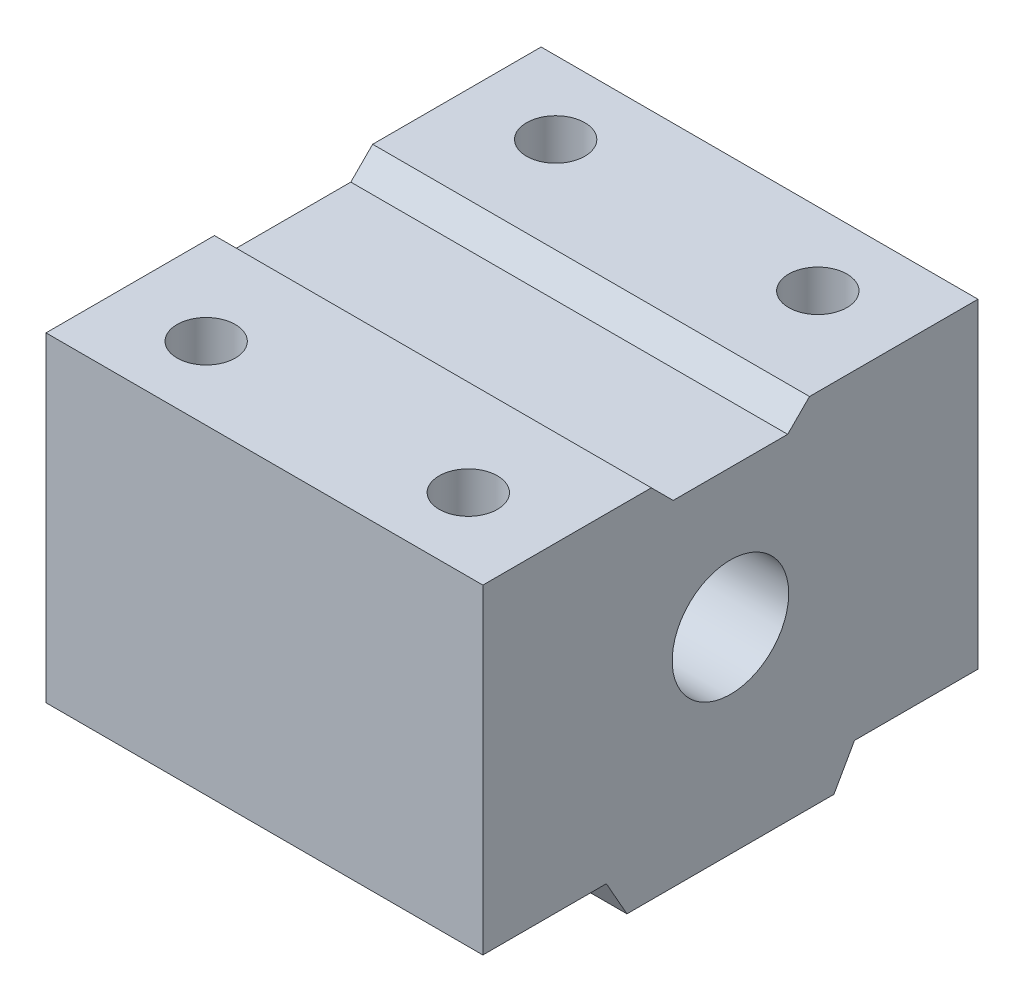
SolidWorks part; units mm, degrees
ref_plane "Front Plane" through (0, 0, 0) normal (0, 0, 1) x (1, 0, 0)
ref_plane "Top Plane" through (0, 0, 0) normal (0, 1, 0) x (1, 0, 0)
ref_plane "Right Plane" through (0, 0, 0) normal (1, 0, 0) x (0, 0, -1)
sketch "Sketch1" plane through (0, 0, 0) normal (0, 1, 0) x (1, 0, 0)
  line L1 (-15, 17) -> (15, 17)
  line L2 (-15, 17) -> (-15, -17)
  line L3 (-15, -17) -> (15, -17)
  line L4 (15, 17) -> (15, -17)
  line L5 (-15, 17) -> (15, -17) construction
  line L6 (-15, -17) -> (15, 17) construction
  point P0 (0, 0)
  dimension "D1" = 30
  dimension "D2" = 34
extrude "Boss-Extrude1" add sketch "Sketch1" along normal blind 22
hole_wizard "Ø4.0mm Dowel Hole1" positions "Sketch2" profile "Sketch3" hole size "Ø4.0" standard "ANSI Metric" end condition up to next
sketch "Sketch2" plane through (0, 22, 0) normal (0, 1, 0) x (1, 0, 0)
  line L0 (-15, 0) -> (15, 0) construction
  line L1 (-15, 17) -> (-15, -17) construction
  line L2 (15, 17) -> (15, -17) construction
  line L4 (0, 0) -> (0, -17) construction
  line L5 (-15, -17) -> (15, -17) construction
  point P0 (9, -12)
  point P2 (-9, -12)
  point P19 (9, 12)
  point P20 (-9, 12)
  dimension "D1" = 12
  dimension "D2" = 12
  dimension "D3" = 9
  dimension "D4" = 9
sketch "Sketch3" plane through (9, 22, 12) normal (1, 0, 0) x (0, 0, 1)
  line L0 (0, 0) -> (0, 22)
  line L1 (0, 22) -> (2, 22)
  line L2 (2, 22) -> (2, 0)
  line L5 (2, 0) -> (0, 0)
  line L11 (0, -6.35) -> (0, 107.95) construction
  dimension "Thru Hole Dia." = 4
  dimension "Thru Hole Depth" = 22
sketch "Sketch4" plane through (15, 0, 0) normal (1, 0, 0) x (0, 0, -1)
  line L0 (-8.5198, 0) -> (8.5198, 0)
  line L1 (-17, 0) -> (17, 0) construction
  line L2 (17, 0) -> (-17, 0) construction
  line L3 (8.5198, 0) -> (7.1062, -2.5)
  line L4 (7.1062, -2.5) -> (-7.1062, -2.5)
  line L5 (0, 0) -> (0, -2.5) construction
  line L6 (-8.5198, 0) -> (-7.1062, -2.5)
  dimension "D1" = 2.5
extrude "Boss-Extrude2" add sketch "Sketch4" against normal through all
sketch "Sketch5" plane through (0, 22, 0) normal (0, 1, 0) x (1, 0, 0)
  line L1 (-15, 5.4305) -> (15, 5.4305)
  line L2 (-15, 5.4305) -> (-15, -5.4305)
  line L3 (-15, -5.4305) -> (15, -5.4305)
  line L4 (15, 5.4305) -> (15, -5.4305)
  line L5 (-15, 5.4305) -> (15, -5.4305) construction
  line L6 (-15, -5.4305) -> (15, 5.4305) construction
  line L7 (15, 17) -> (15, -17) construction
extrude "Cut-Extrude1" cut sketch "Sketch5" against normal blind 1.5
chamfer "Chamfer2" distance 1.5 angle 45 2 edges at (0, 20.5, 5.4305) (0, 20.5, -5.4305) tangent propagation no
sketch "Sketch6" plane through (0, 22, 0) normal (0, 1, 0) x (1, 0, 0)
  line L0 (-15, -17) -> (15, -17) construction
  line L1 (15, 17) -> (15, -17) construction
  line L2 (-15, 17) -> (-15, -17) construction
  line L3 (-15, 17) -> (15, 17) construction
  line L4 (-15, -17) -> (15, -17)
  line L5 (15, 17) -> (15, -17)
  line L6 (-15, 17) -> (-15, -17)
  line L7 (-15, 17) -> (15, 17)
  circle A0 centre (9, -12) radius 2 construction
  circle A1 centre (-9, -12) radius 2 construction
  circle A2 centre (-9, 12) radius 2 construction
  circle A3 centre (9, 12) radius 2 construction
  circle A4 centre (9, -12) radius 2
  circle A5 centre (-9, -12) radius 2
  circle A6 centre (-9, 12) radius 2
  circle A7 centre (9, 12) radius 2
sketch "Sketch8" plane through (15, 0, 0) normal (1, 0, 0) x (0, 0, -1)
  line L0 (0, 11) -> (-17, 11) construction
  line L1 (-17, 22) -> (-17, 0) construction
  line L2 (0, 11) -> (17, 11) construction
  line L3 (17, 22) -> (17, 0) construction
  circle A0 centre (0, 11) radius 4
  dimension "D1" = 8
extrude "Cut-Extrude2" cut sketch "Sketch8" against normal through all contours L2 A0 L0 | L0 A0 L2 region at (15, 9.3023, 0) region at (15, 12.6977, 0)
equation "\"Width\"= 30"
equation "\"Length\"= 34"
equation "\"Height\"= 22"
equation "\"Center Distance\"= 24"
equation "\"Center Distance 2\"= 18"
equation "\"D1@Sketch1\"=\"Width\""
equation "\"D2@Sketch1\"=\"Length\""
equation "\"D1@Boss-Extrude1\"=\"Height\""
equation "\"D1@Sketch2\"=\"Center Distance\"/2"
equation "\"D2@Sketch2\"=\"D1@Sketch2\""
equation "\"D3@Sketch2\"=\"Center Distance 2\"/2"
equation "\"D4@Sketch2\"=\"Center Distance 2\"/2"
